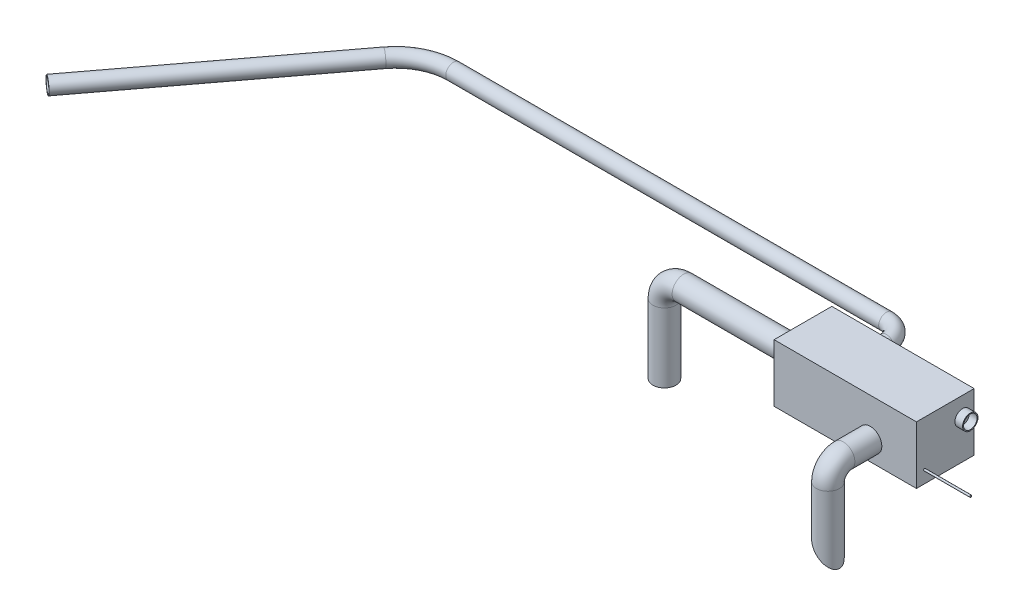
SolidWorks part; units mm, degrees
ref_plane "Front" through (0, 0, 0) normal (0, 0, 1) x (1, 0, 0)
ref_plane "Top" through (0, 0, 0) normal (0, 1, 0) x (1, 0, 0)
ref_plane "Right" through (0, 0, 0) normal (1, 0, 0) x (0, 0, -1)
sketch "Sketch1" plane through (0, 0, 0) normal (0, 1, 0) x (1, 0, 0)
  line L1 (-469.9, 190.5) -> (469.9, 190.5)
  line L2 (-469.9, 190.5) -> (-469.9, -190.5)
  line L3 (-469.9, -190.5) -> (469.9, -190.5)
  line L4 (469.9, 190.5) -> (469.9, -190.5)
  line L5 (-469.9, 190.5) -> (469.9, -190.5) construction
  line L6 (-469.9, -190.5) -> (469.9, 190.5) construction
  point P0 (0, 0)
  dimension "D1" = 381
  dimension "D2" = 939.8
extrude "Boss-Extrude1" add sketch "Sketch1" along normal blind 381
sketch "Sketch2" plane through (0, 0, 190.5) normal (0, 0, 1) x (1, 0, 0)
  line L0 (469.9, 381) -> (469.9, 0) construction
  line L1 (-469.9, 381) -> (469.9, 381) construction
  circle A0 centre (165.1, 127) radius 76.2
  circle A1 centre (165.1, 127) radius 69.85
  dimension "D1" = 152.4
  dimension "D3" = 254
  dimension "D4" = 139.7
  dimension "D2" = 304.8
extrude "Boss-Extrude2" add sketch "Sketch2" along normal blind 152.4
sketch "Sketch3" plane through (469.9, 0, 0) normal (1, 0, 0) x (0, 0, -1)
  line L0 (-190.5, 381) -> (190.5, 381) construction
  line L1 (190.5, 381) -> (190.5, 0) construction
  circle A0 centre (114.3, 254) radius 50.8
  circle A1 centre (114.3, 254) radius 44.45
  dimension "D1" = 101.6
  dimension "D2" = 88.9
  dimension "D3" = 127
  dimension "D4" = 76.2
extrude "Boss-Extrude3" add sketch "Sketch3" along normal blind 50.8
sketch "Sketch4" plane through (469.9, 0, 0) normal (1, 0, 0) x (0, 0, -1)
  circle A0 centre (-136.8501, 81.3511) radius 6.35
  dimension "D1" = 12.7
extrude "Boss-Extrude4" add sketch "Sketch4" along normal blind 304.8
sketch "Sketch5" plane through (0, 0, -190.5) normal (0, 0, -1) x (-1, 0, 0)
  line L0 (-469.9, 381) -> (469.9, 381) construction
  line L1 (469.9, 381) -> (469.9, 0) construction
  circle A0 centre (185.6926, 273.8882) radius 50.8
  circle A1 centre (185.6926, 273.8882) radius 44.45
  dimension "D1" = 101.6
  dimension "D2" = 88.9
  dimension "D4" = 284.2074
  dimension "D3" = 107.1118
extrude "Boss-Extrude5" add sketch "Sketch5" along normal blind 50.8
sketch "Sketch6" plane through (-469.9, 0, 0) normal (-1, 0, 0) x (0, 0, 1)
  line L0 (-190.5, 381) -> (190.5, 0) construction
  circle A0 centre (0, 190.5) radius 76.2
  circle A1 centre (0, 190.5) radius 69.85
  dimension "D1" = 152.4
  dimension "D2" = 139.7
extrude "Boss-Extrude6" add sketch "Sketch6" along normal blind 762
sketch "Sketch7" plane through (0, 0, 342.9) normal (0, 0, 1) x (1, 0, 0)
  circle A0 centre (165.1, 127) radius 76.2 construction
  circle A1 centre (165.1, 127) radius 76.2
  circle A2 centre (165.1, 127) radius 69.85 construction
  circle A3 centre (165.1, 127) radius 69.85
ref_point "Point1"
ref_plane "Plane1" through (165.1, 0, 0) normal (1, 0, 0) x (0, 0, -1)
sketch "Sketch8" plane through (165.1, 0, 0) normal (1, 0, 0) x (0, 0, -1)
  line L0 (-342.9, 127) -> (-368.3, 127)
  line L1 (-342.9, 203.2) -> (-342.9, 50.8) construction
  line L2 (-469.9, 25.4) -> (-469.9, -431.8)
  arc A0 (-368.3, 127) -> (-469.9, 25.4) centre (-368.3, 25.4) ccw
  dimension "D3" = 101.6
  dimension "D1" = 457.2
  dimension "D2" = 25.4
sweep "Sweep1" add profiles "Sketch7" path "Sketch8"
ref_point "Point2"
ref_plane "Plane2" through (0, 190.5, 0) normal (0, 1, 0) x (1, 0, 0)
sketch "Sketch9" plane through (0, 190.5, 0) normal (0, 1, 0) x (1, 0, 0)
  line L0 (-1231.9, 0) -> (-4279.9, 0)
  line L1 (-1231.9, 76.2) -> (-1231.9, -76.2) construction
  dimension "D1" = 3048
sketch "Sketch10" plane through (-1231.9, 0, 0) normal (-1, 0, 0) x (0, 0, 1)
  circle A0 centre (0, 190.5) radius 76.2 construction
  circle A1 centre (0, 190.5) radius 76.2
  circle A2 centre (0, 190.5) radius 69.85 construction
  circle A3 centre (0, 190.5) radius 69.85
sweep "Sweep2" [suppressed] add profiles "Sketch10" path "Sketch9"
ref_point "Point5"
ref_plane "Plane5" through (0, 273.8882, 0) normal (0, 1, 0) x (1, 0, 0)
sketch "Sketch13" plane through (0, 273.8882, 0) normal (0, 1, 0) x (1, 0, 0)
  line L0 (-185.6926, 241.3) -> (-185.6926, 266.7)
  line L1 (-134.8926, 241.3) -> (-236.4926, 241.3) construction
  line L2 (-181.0972, 292.7619) -> (330.9506, 1699.6019)
  line L3 (340.1415, 1751.7257) -> (340.1415, 2867.8535)
  line L4 (469.9, 190.5) -> (-469.9, 190.5) construction
  arc A0 (-185.6926, 266.7) -> (-181.0972, 292.7619) centre (-109.4926, 266.7) cw
  arc A1 (340.1415, 1751.7257) -> (330.9506, 1699.6019) centre (187.7415, 1751.7257) cw
  point P13 (340.1415, 1724.8535)
  dimension "D1" = 76.2
  dimension "D6" = 152.4
  dimension "D2" = 25.4
  dimension "D3" = 1524
  dimension "D4" = 1143
  dimension "D5" = 70
sketch "Sketch14" plane through (0, 0, -241.3) normal (0, 0, -1) x (-1, 0, 0)
  circle A0 centre (185.6926, 273.8882) radius 44.45 construction
  circle A1 centre (185.6926, 273.8882) radius 50.8
  circle A2 centre (185.6926, 273.8882) radius 50.8
  circle A3 centre (185.6926, 273.8882) radius 44.45
  dimension "D1" = 0
sweep "Sweep5" [suppressed] add profiles "Sketch14" path "Sketch13"
sketch "Sketch15" plane through (0, 273.8882, 0) normal (0, 1, 0) x (1, 0, 0)
  line L0 (-185.6926, 241.3) -> (-185.6926, 317.5)
  line L1 (-134.8926, 241.3) -> (-236.4926, 241.3) construction
  line L4 (2989.3074, 444.5) -> (-58.6926, 444.5)
  arc A0 (-185.6926, 317.5) -> (-58.6926, 444.5) centre (-58.6926, 317.5) cw
  dimension "D2" = 127
  dimension "D1" = 76.2
  dimension "D5" = 3048
sketch "Sketch16" plane through (0, 0, -241.3) normal (0, 0, -1) x (-1, 0, 0)
  circle A0 centre (185.6926, 273.8882) radius 44.45 construction
  circle A1 centre (185.6926, 273.8882) radius 50.8
  circle A2 centre (185.6926, 273.8882) radius 50.8
  circle A3 centre (185.6926, 273.8882) radius 44.45
  dimension "D1" = 0
sweep "Sweep6" [suppressed] add profiles "Sketch16" path "Sketch15"
sketch "Sketch22" plane through (0, 0, 190.5) normal (0, 0, 1) x (1, 0, 0)
  line L0 (88.9, -279.4) -> (241.3, -431.8)
  line L1 (88.9, 25.4) -> (88.9, -431.8) construction
  line L2 (241.3, -431.8) -> (88.9, -431.8)
  line L3 (88.9, -431.8) -> (88.9, -279.4)
  dimension "D1" = 45
extrude "Cut-Extrude3" cut sketch "Sketch22" along normal through all
sketch "Sketch23" [suppressed] plane through (2989.3074, 0, 0) normal (1, 0, 0) x (0, 0, -1)
  circle A0 centre (444.5, 273.8882) radius 44.45 construction
  circle A1 centre (444.5, 273.8882) radius 50.8
  circle A2 centre (444.5, 273.8882) radius 50.8
  circle A3 centre (444.5, 273.8882) radius 44.45
  dimension "D1" = 0
sketch "Sketch24" [suppressed] plane through (0, 190.5, 0) normal (0, 1, 0) x (1, 0, 0)
  line L0 (2989.3074, 444.5) -> (2735.3074, 444.5)
  line L1 (2989.3074, 393.7) -> (2989.3074, 495.3) construction
  line L2 (2481.3074, 376.4409) -> (2041.3664, 122.4409)
  arc A0 (2735.3074, 444.5) -> (2481.3074, 376.4409) centre (2735.3074, -63.5) ccw
  dimension "D1" = 508
  dimension "D2" = 254
  dimension "D3" = 150
  dimension "D4" = 508
sweep "Sweep7" [suppressed] add profiles "Sketch23" path "Sketch24"
sketch "Sketch25" [suppressed] plane through (-3771.9, 0, 0) normal (-1, 0, 0) x (0, 0, 1)
  circle A0 centre (0, 190.5) radius 69.85 construction
  circle A1 centre (0, 190.5) radius 76.2
  circle A2 centre (0, 190.5) radius 76.2
  circle A3 centre (0, 190.5) radius 69.85
  dimension "D1" = 0
ref_plane "Plane6" through (0, 0, 0) normal (0, 0, 1) x (1, 0, 0)
sketch "Sketch26" plane through (0, 0, 0) normal (0, 0, 1) x (1, 0, 0)
  line L0 (-1231.9, 190.5) -> (-1257.3, 190.5)
  line L1 (-1231.9, 266.7) -> (-1231.9, 114.3) construction
  line L2 (-1384.3, 63.5) -> (-1384.3, -393.7)
  arc A0 (-1257.3, 190.5) -> (-1384.3, 63.5) centre (-1257.3, 63.5) ccw
  dimension "D1" = 127
  dimension "D2" = 25.4
  dimension "D3" = 457.2
sketch "Sketch27" plane through (-1231.9, 0, 0) normal (-1, 0, 0) x (0, 0, 1)
  circle A0 centre (0, 190.5) radius 76.2 construction
  circle A1 centre (0, 190.5) radius 76.2
  circle A3 centre (0, 190.5) radius 69.85 construction
  circle A4 centre (0, 190.5) radius 69.85
sweep "Sweep8" add profiles "Sketch27" path "Sketch26"
sketch "Sketch28" plane through (0, 273.8882, 0) normal (0, 1, 0) x (1, 0, 0)
  line L0 (-185.6926, 241.3) -> (-185.6926, 266.7)
  line L1 (-134.8926, 241.3) -> (-236.4926, 241.3) construction
  line L2 (-312.6926, 393.7) -> (-3170.7331, 393.7)
  line L3 (-3475.0132, 241.9915) -> (-4430.7198, -1026.2739)
  arc A0 (-185.6926, 266.7) -> (-312.6926, 393.7) centre (-312.6926, 266.7) ccw
  arc A1 (-3170.7331, 393.7) -> (-3475.0132, 241.9915) centre (-3170.7331, 12.7) ccw
  point P10 (-3360.6926, 393.7)
  dimension "D1" = 127
  dimension "D6" = 381
  dimension "D2" = 3048
  dimension "D3" = 25.4
  dimension "D4" = 127
  dimension "D5" = 1778
sketch "Sketch29" plane through (0, 0, -241.3) normal (0, 0, -1) x (-1, 0, 0)
  circle A0 centre (185.6926, 273.8882) radius 44.45 construction
  circle A1 centre (185.6926, 273.8882) radius 50.8
  circle A2 centre (185.6926, 273.8882) radius 50.8
  circle A3 centre (185.6926, 273.8882) radius 44.45
  dimension "D1" = 0
sweep "Sweep9" add profiles "Sketch29" path "Sketch28"
